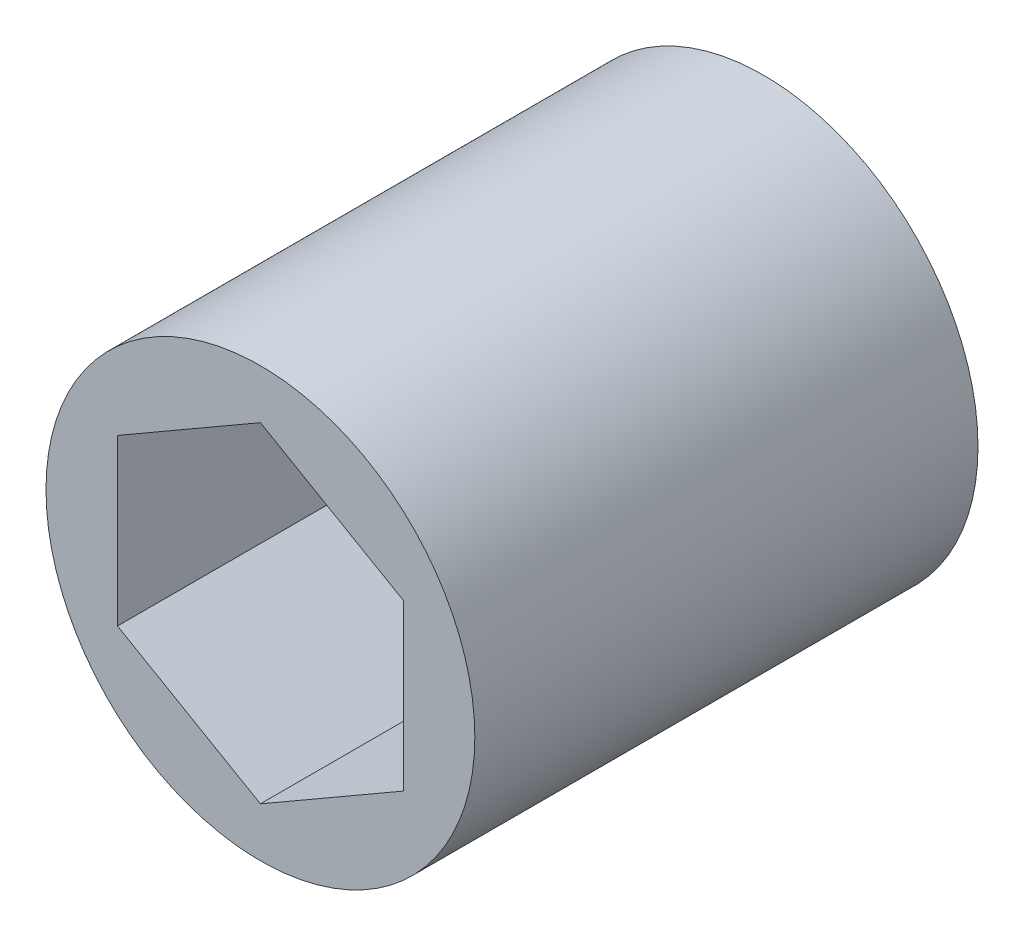
SolidWorks part; units mm, degrees
ref_plane "Front Plane" through (0, 0, 0) normal (0, 0, 1) x (1, 0, 0)
ref_plane "Top Plane" through (0, 0, 0) normal (0, 1, 0) x (1, 0, 0)
ref_plane "Right Plane" through (0, 0, 0) normal (1, 0, 0) x (0, 0, -1)
sketch "Sketch1" plane through (0, 0, 0) normal (0, 0, 1) x (1, 0, 0)
  line L1 (0, 7.3323) -> (-6.35, 3.6662)
  line L2 (-6.35, 3.6662) -> (-6.35, -3.6662)
  line L3 (-6.35, -3.6662) -> (0, -7.3323)
  line L4 (0, -7.3323) -> (6.35, -3.6662)
  line L5 (6.35, -3.6662) -> (6.35, 3.6662)
  line L6 (6.35, 3.6662) -> (0, 7.3323)
  circle A0 centre (0, 0) radius 9.525
  circle A1 centre (0, 0) radius 6.35 construction
  point P3 (0, 0)
  dimension "D1" = 19.05
  dimension "D2" = 12.7
extrude "Boss-Extrude1" add sketch "Sketch1" along normal blind 22.352
